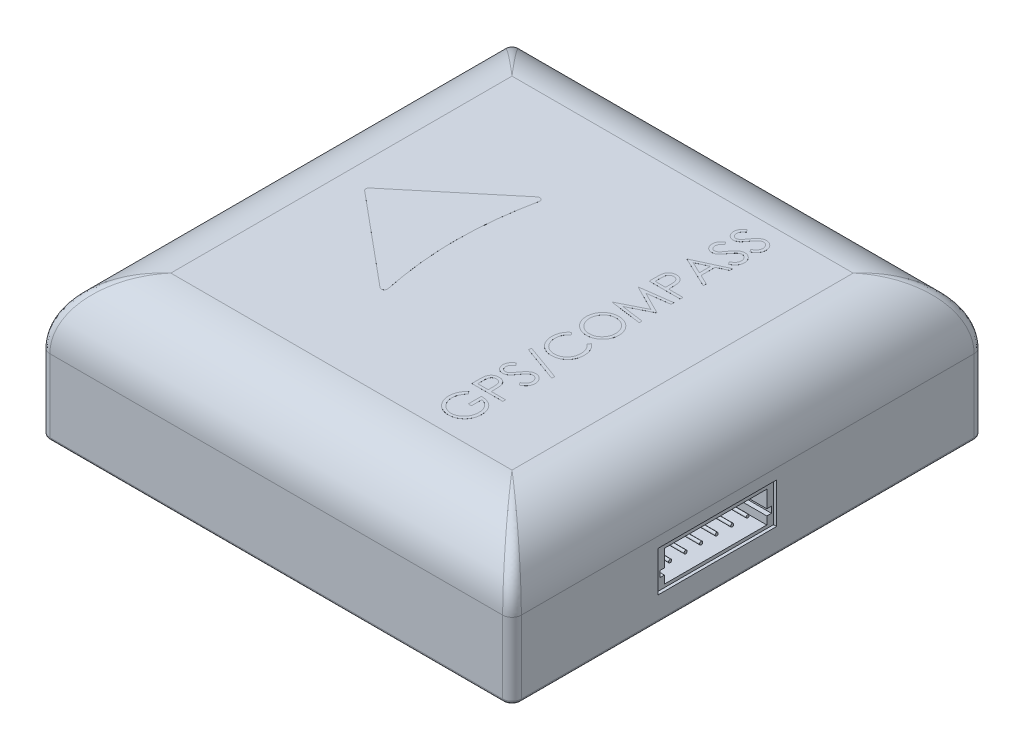
SolidWorks part; units mm, degrees
ref_plane "Front" through (0, 0, 0) normal (0, 0, 1) x (1, 0, 0)
ref_plane "Top" through (0, 0, 0) normal (0, 1, 0) x (1, 0, 0)
ref_plane "Right" through (0, 0, 0) normal (1, 0, 0) x (0, 0, -1)
sketch "Sketch1" plane through (0, 0, 0) normal (0, 1, 0) x (1, 0, 0)
  line L1 (-19.304, -19.304) -> (19.304, -19.304)
  line L2 (-19.304, -19.304) -> (-19.304, 19.304)
  line L3 (-19.304, 19.304) -> (19.304, 19.304)
  line L4 (19.304, -19.304) -> (19.304, 19.304)
  line L5 (-19.304, -19.304) -> (19.304, 19.304) construction
  line L6 (-19.304, 19.304) -> (19.304, -19.304) construction
  point P0 (0, 0)
  dimension "D1" = 38.608
  dimension "D2" = 38.608
extrude "Boss-Extrude1" add sketch "Sketch1" along normal mid plane 11.5316
sketch "Sketch2" plane through (19.304, 0, 0) normal (1, 0, 0) x (0, 0, -1)
  line L0 (-19.304, 5.7658) -> (-19.304, -5.7658) construction
  line L1 (-7.366, -0.4318) -> (2.3622, -0.4318)
  line L2 (-7.366, -0.4318) -> (-7.366, -3.7338)
  line L3 (-7.366, -3.7338) -> (2.3622, -3.7338)
  line L4 (2.3622, -0.4318) -> (2.3622, -3.7338)
  line L5 (-19.304, -5.7658) -> (19.304, -5.7658) construction
  dimension "D1" = 11.938
  dimension "D2" = 9.7282
  dimension "D3" = 3.302
  dimension "D4" = 2.032
extrude "Cut-Extrude1" cut sketch "Sketch2" against normal blind 5.08
fillet "Fillet1" radius 5.334 4 edges at (0, 5.7658, 19.304) (-19.304, 5.7658, 0) (0, 5.7658, -19.304) (19.304, 5.7658, 0)
fillet "Fillet2" radius 0.762 8 edges at (17.7417, 4.2035, -17.7417) (-17.7417, 4.2035, -17.7417) (-17.7417, 4.2035, 17.7417) (17.7417, 4.2035, 17.7417) (19.304, -2.667, -19.304) (-19.304, -2.667, -19.304) (-19.304, -2.667, 19.304) (19.304, -2.667, 19.304)
fillet "Fillet3" radius 0.254 8 edges at (-19.0808, -5.7658, -19.0808) (-19.304, -5.7658, 0) (-19.0808, -5.7658, 19.0808) (0, -5.7658, 19.304) (19.0808, -5.7658, 19.0808) (19.304, -5.7658, 0) (19.0808, -5.7658, -19.0808) (0, -5.7658, -19.304)
sketch "Sketch3" plane through (14.224, 0, 0) normal (1, 0, 0) x (0, 0, -1)
  line L4 (-2.5019, -0.4318) -> (-2.5019, -3.7338) construction
  line L5 (-6.6929, -0.8128) -> (1.6891, -0.8128)
  line L6 (-6.6929, -0.8128) -> (-6.6929, -2.2054)
  line L7 (-6.6929, -3.3528) -> (1.6891, -3.3528)
  line L8 (-7.239, -0.5588) -> (-7.239, -3.6068)
  line L9 (-7.239, -3.6068) -> (2.2352, -3.6068)
  line L10 (2.2352, -3.6068) -> (2.2352, -0.5588)
  line L11 (2.2352, -0.5588) -> (-7.239, -0.5588)
  line L12 (-7.239, -0.5588) -> (-7.239, -3.6068)
  line L13 (-7.239, -3.6068) -> (2.2352, -3.6068)
  line L14 (2.2352, -3.6068) -> (2.2352, -0.5588)
  line L15 (2.2352, -0.5588) -> (-7.239, -0.5588)
  line L16 (1.6891, -0.8128) -> (1.6891, -2.2054)
  line L17 (2.3622, -0.4318) -> (-7.366, -0.4318) construction
  line L18 (-7.366, -3.7338) -> (2.3622, -3.7338) construction
  line L19 (2.0701, -2.2054) -> (2.0701, -2.7134)
  line L20 (-6.6929, -2.2054) -> (-7.0739, -2.2054)
  line L21 (1.6891, -2.7134) -> (1.6891, -3.3528)
  line L22 (-6.6929, -2.7134) -> (-7.0739, -2.7134)
  line L23 (-7.0739, -2.2054) -> (-7.0739, -2.7134)
  line L24 (1.6891, -2.7134) -> (2.0701, -2.7134)
  line L26 (1.6891, -2.2054) -> (2.0701, -2.2054)
  line L27 (-6.6929, -2.7134) -> (-6.6929, -3.3528)
  point P8 (-2.5019, -0.8128)
  point P9 (-2.5019, -0.5588)
  dimension "D2" = 0.254
  dimension "D3" = 0.254
  dimension "D4" = 8.382
  dimension "D5" = 0.381
  dimension "D6" = 0.508
  dimension "D1" = 0.127
extrude "Boss-Extrude2" add sketch "Sketch3" along normal offset from surface (4.953 mm away) 0.127 up to face at (19.304, -2.0828, 2.5019)
sketch "Sketch4" plane through (14.224, 0, 0) normal (1, 0, 0) x (0, 0, -1)
  line L0 (-7.0739, -2.2054) -> (-7.0739, -2.7134) construction
  circle A0 centre (-5.7192, -2.4594) radius 0.127
  circle A1 centre (-4.4492, -2.4594) radius 0.127
  circle A2 centre (-3.1792, -2.4594) radius 0.127
  circle A3 centre (-1.9092, -2.4594) radius 0.127
  circle A4 centre (-0.6392, -2.4594) radius 0.127
  circle A5 centre (0.6308, -2.4594) radius 0.127
  point P15 (-7.0739, -2.4594)
  dimension "D1" = 0.254
  dimension "D3" = 1.27
  dimension "D2" = 6
extrude "Boss-Extrude3" add sketch "Sketch4" along normal offset from surface (4.445 mm away) 0.508 up to face at (19.177, -2.3339, 2.5019)
sketch "Sketch5" plane through (0, -5.7658, 0) normal (0, -1, 0) x (1, 0, 0)
  circle A0 centre (0, 0) radius 1.5423
split line "Split Line1"
sketch "Sketch6" plane through (0, 5.7658, 0) normal (0, 1, 0) x (1, 0, 0)
  line L0 (8.7262, 13.97) -> (8.7262, -13.97) construction
  line L1 (13.97, 13.97) -> (-13.97, 13.97) construction
  line L2 (-13.97, -13.97) -> (13.97, -13.97) construction
  line L3 (0, 0) -> (-13.97, 0) construction
  line L4 (-13.97, 13.97) -> (-13.97, -13.97) construction
  line L5 (-11.8697, 0.1952) -> (-4.378, 6.4289)
  line L6 (-11.8697, -0.1952) -> (-4.378, -6.4289)
  arc A0 (-4.378, 6.4289) -> (-3.9669, 6.1817) centre (-4.2155, 6.2336) cw
  arc A1 (-4.378, -6.4289) -> (-3.9669, -6.1817) centre (-4.2155, -6.2336) ccw
  arc A2 (-11.8697, 0.1952) -> (-11.8697, -0.1952) centre (-11.7073, 0) ccw
  spline S0 degree 3 poles (-3.9669, 6.1817) (-4.3953, 4.1303) (-4.6293, 2.0917) (-4.6293, 0) knots 0.114382 0.114382 0.114382 0.114382 1 1 1 1
  spline S1 degree 3 poles (-3.9669, -6.1817) (-4.3953, -4.1303) (-4.6293, -2.0917) (-4.6293, 0) knots 0.114382 0.114382 0.114382 0.114382 1 1 1 1
  text T0 "GPS/COMPASS" font "Century Gothic" height 2.54
  point P22 (-12.1044, 0)
  dimension "D1" = 0.254
  dimension "D2" = 0.254
extrude "Boss-Extrude4" add sketch "Sketch6" along normal blind 0.0025
